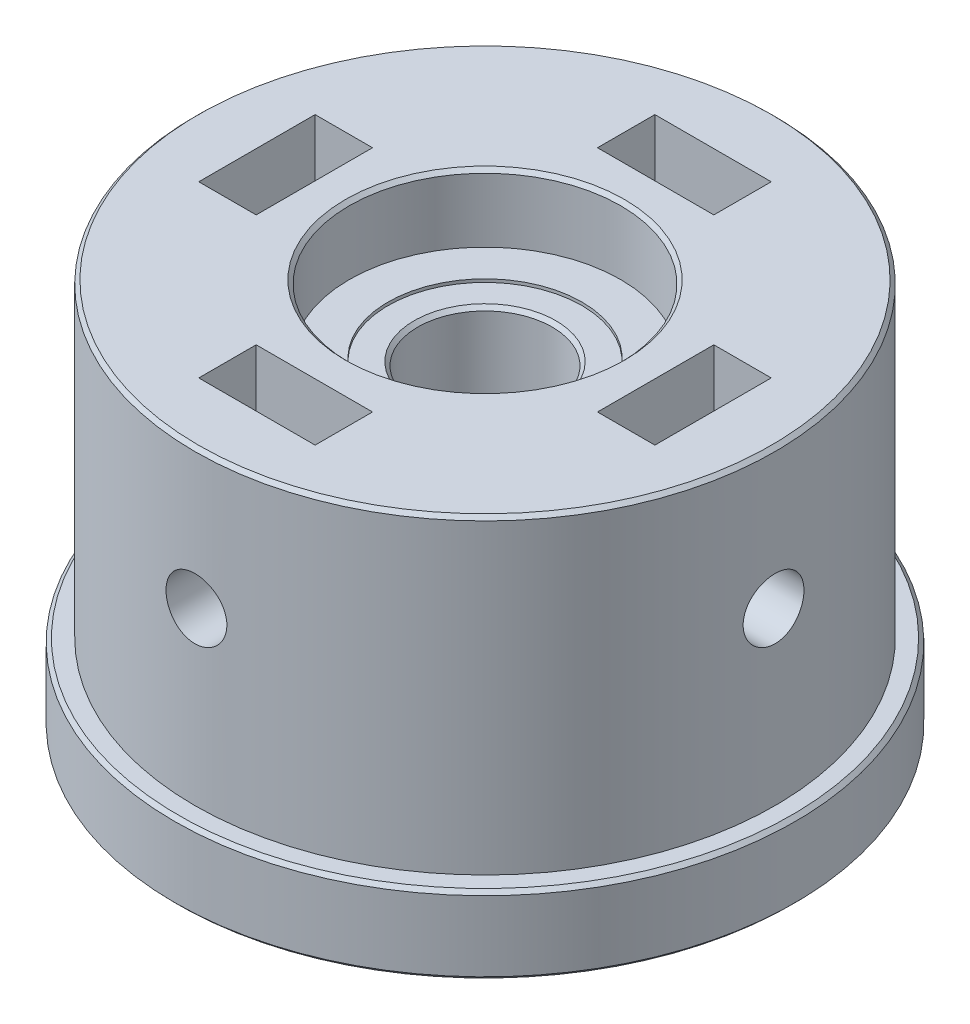
SolidWorks part; units mm, degrees
material "Nylon 101"
ref_plane "Front Plane" through (0, 0, 0) normal (0, 0, 1) x (1, 0, 0)
ref_plane "Top Plane" through (0, 0, 0) normal (0, 1, 0) x (1, 0, 0)
ref_plane "Right Plane" through (0, 0, 0) normal (1, 0, 0) x (0, 0, -1)
sketch "Sketch1" plane through (0, 0, 0) normal (0, 1, 0) x (1, 0, 0)
  circle A0 centre (0, 0) radius 23.749
  dimension "D1" = 47.498
extrude "Boss-Extrude1" add sketch "Sketch1" along normal blind 25.4
sketch "Sketch2" plane through (0, 0, 0) normal (0, -1, 0) x (1, 0, 0)
  circle A0 centre (0, 0) radius 25.4
  dimension "D1" = 50.8
extrude "Boss-Extrude2" add sketch "Sketch2" along normal blind 6.35
sketch "Sketch3" plane through (0, -6.35, 0) normal (0, -1, 0) x (1, 0, 0)
  circle A0 centre (0, 0) radius 5.5
  dimension "D1" = 11
extrude "Cut-Extrude1" cut sketch "Sketch3" against normal through all
sketch "Sketch4" plane through (0, -6.35, 0) normal (0, -1, 0) x (1, 0, 0)
  circle A0 centre (0, 0) radius 11.1125
  dimension "D1" = 22.225
extrude "Cut-Extrude2" cut sketch "Sketch4" against normal blind 5.5372
sketch "Sketch5" plane through (0, -0.8128, 0) normal (0, -1, 0) x (1, 0, 0)
  circle A0 centre (0, 0) radius 7.9375
  dimension "D1" = 15.875
extrude "Cut-Extrude3" cut sketch "Sketch5" against normal blind 0.254
ref_plane "Plane1" through (0, 9.525, 0) normal (0, 1, 0) x (1, 0, 0)
mirror "Mirror1" about plane through (0, 9.525, 0) normal (0, 1, 0) of "Cut-Extrude2", "Cut-Extrude3"
chamfer "Chamfer1" distance 0.3 angle 45 7 edges at (0, 0, -25.4) (0, -6.35, -25.4) (0, -6.35, -11.1125) (0, 25.4, 23.749) (0, 19.6088, 5.5) (0, -0.5588, -5.5) (0, 25.4, -11.1125)
sketch "Sketch6" plane through (0, 0, 0) normal (0, 0, 1) x (1, 0, 0)
  line L1 (23.449, 25.4) -> (-23.449, 25.4) construction
  circle A0 centre (0, 13.97) radius 2.4892
  dimension "D1" = 4.9784
  dimension "D2" = 11.43
sketch "Sketch7" plane through (0, 0, 0) normal (1, 0, 0) x (0, 0, -1)
  line L0 (0, 16.4592) -> (0, 11.4808) construction
  circle A0 centre (0, 13.97) radius 2.4892
  dimension "D1" = 4.9784
sketch "Sketch8" plane through (0, 25.4, 0) normal (0, 1, 0) x (1, 0, 0)
  line L0 (18.669, 4.7625) -> (18.669, -4.7625)
  line L1 (-4.7625, 13.97) -> (4.7625, 13.97)
  line L2 (-4.7625, 13.97) -> (-4.7625, 18.669)
  line L3 (-4.7625, 18.669) -> (4.7625, 18.669)
  line L4 (4.7625, 13.97) -> (4.7625, 18.669)
  line L5 (-4.7625, 13.97) -> (4.7625, 18.669) construction
  line L6 (-4.7625, 18.669) -> (4.7625, 13.97) construction
  line L7 (13.97, 4.7625) -> (18.669, 4.7625)
  line L8 (13.97, 4.7625) -> (13.97, -4.7625)
  line L9 (13.97, -4.7625) -> (18.669, -4.7625)
  line L10 (4.7625, -18.669) -> (-4.7625, -18.669)
  line L11 (4.7625, -13.97) -> (4.7625, -18.669)
  line L12 (4.7625, -13.97) -> (-4.7625, -13.97)
  line L13 (-4.7625, -13.97) -> (-4.7625, -18.669)
  line L14 (-18.669, -4.7625) -> (-18.669, 4.7625)
  line L15 (-13.97, -4.7625) -> (-18.669, -4.7625)
  line L16 (-13.97, -4.7625) -> (-13.97, 4.7625)
  line L17 (-13.97, 4.7625) -> (-18.669, 4.7625)
  point P0 (0, 16.3195)
  point P21 (0, 0)
  dimension "D1" = 4.699
  dimension "D2" = 9.525
  dimension "D3" = 13.97
  dimension "D4" = 4
extrude "Cut-Extrude4" cut sketch "Sketch8" against normal blind 16.1925
ref_plane "Plane2" through (0, 0, 25.4) normal (0, 0, 1) x (1, 0, 0)
sketch "Sketch9" plane through (0, 0, 25.4) normal (0, 0, 1) x (1, 0, 0)
  circle A0 centre (0, 13.97) radius 2.4892 construction
  circle A1 centre (0, 13.97) radius 2.4892
extrude "Cut-Extrude5" cut sketch "Sketch9" against normal blind 7.62
ref_plane "Plane3" through (25.4, 0, 0) normal (1, 0, 0) x (0, 0, -1)
sketch "Sketch10" plane through (25.4, 0, 0) normal (1, 0, 0) x (0, 0, -1)
  circle A0 centre (0, 13.97) radius 2.4892 construction
  circle A1 centre (0, 13.97) radius 2.4892
extrude "Cut-Extrude6" cut sketch "Sketch10" against normal blind 7.62
mirror "Mirror2" about plane through (0, 0, 0) normal (0, 0, 1) of "Cut-Extrude5"
mirror "Mirror3" about plane through (0, 0, 0) normal (1, 0, 0) of "Cut-Extrude6"
equation "\"D1@Chamfer1\"=.3mm"
